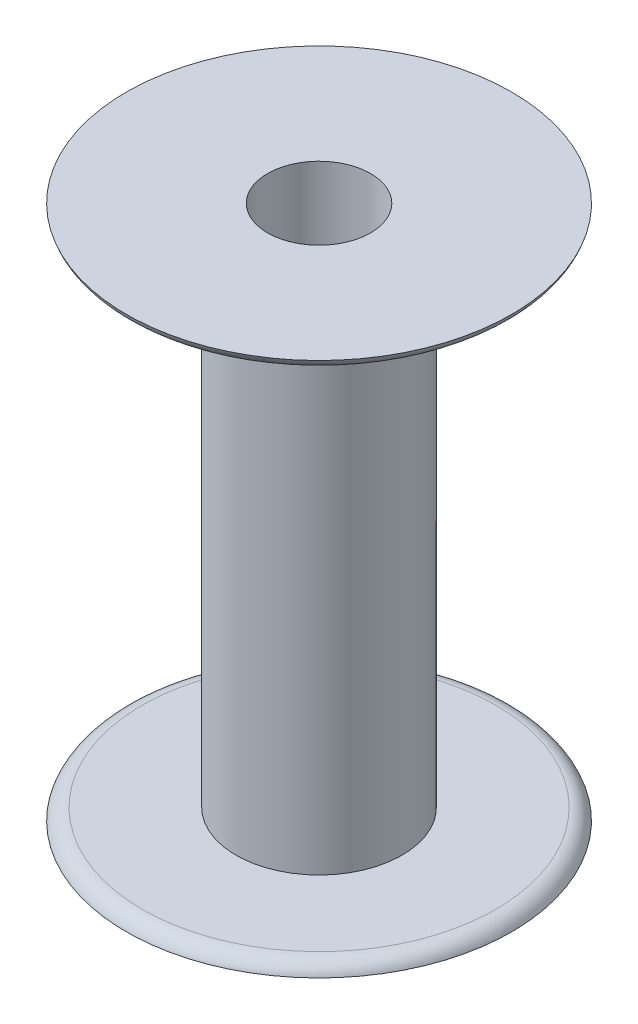
SolidWorks part; units mm, degrees
ref_plane "Front Plane" through (0, 0, 0) normal (0, 0, 1) x (1, 0, 0)
ref_plane "Top Plane" through (0, 0, 0) normal (0, 1, 0) x (1, 0, 0)
ref_plane "Right Plane" through (0, 0, 0) normal (1, 0, 0) x (0, 0, -1)
sketch "Sketch1" plane through (0, 0, 0) normal (0, 0, 1) x (1, 0, 0)
  line L0 (0, 0) -> (0, 16.1)
  line L1 (0, 16.1) -> (11.6, 16.1)
  line L2 (11.6, 16.1) -> (11.6, 15.4)
  line L3 (11.6, 15.4) -> (5, 15.4)
  line L4 (5, 15.4) -> (5, 0)
  line L5 (5, 0) -> (0, 0)
  line L6 (0, 24.3586) -> (0, 25591.8782) construction
  line L7 (0, 0) -> (21.1927, 0) construction
  dimension "D1" = 23.2
  dimension "D2" = 10
  dimension "D3" = 0.7
  dimension "D4" = 32.2
revolve "Revolve1" add sketch "Sketch1" angle 360 about L6
mirror "Mirror1" about plane through (5, 0, 0) normal (0, -1, 0) of bodies 101
sketch "Sketch2" plane through (0, 16.1, 0) normal (0, 1, 0) x (1, 0, 0)
  circle A0 centre (0, 0) radius 3.1
  dimension "D1" = 6.2
extrude "Cut-Extrude1" cut sketch "Sketch2" against normal through all
fillet "Fillet1" radius 1 2 edges at (0, -15.4, -11.6) (0, 15.4, -11.6)
